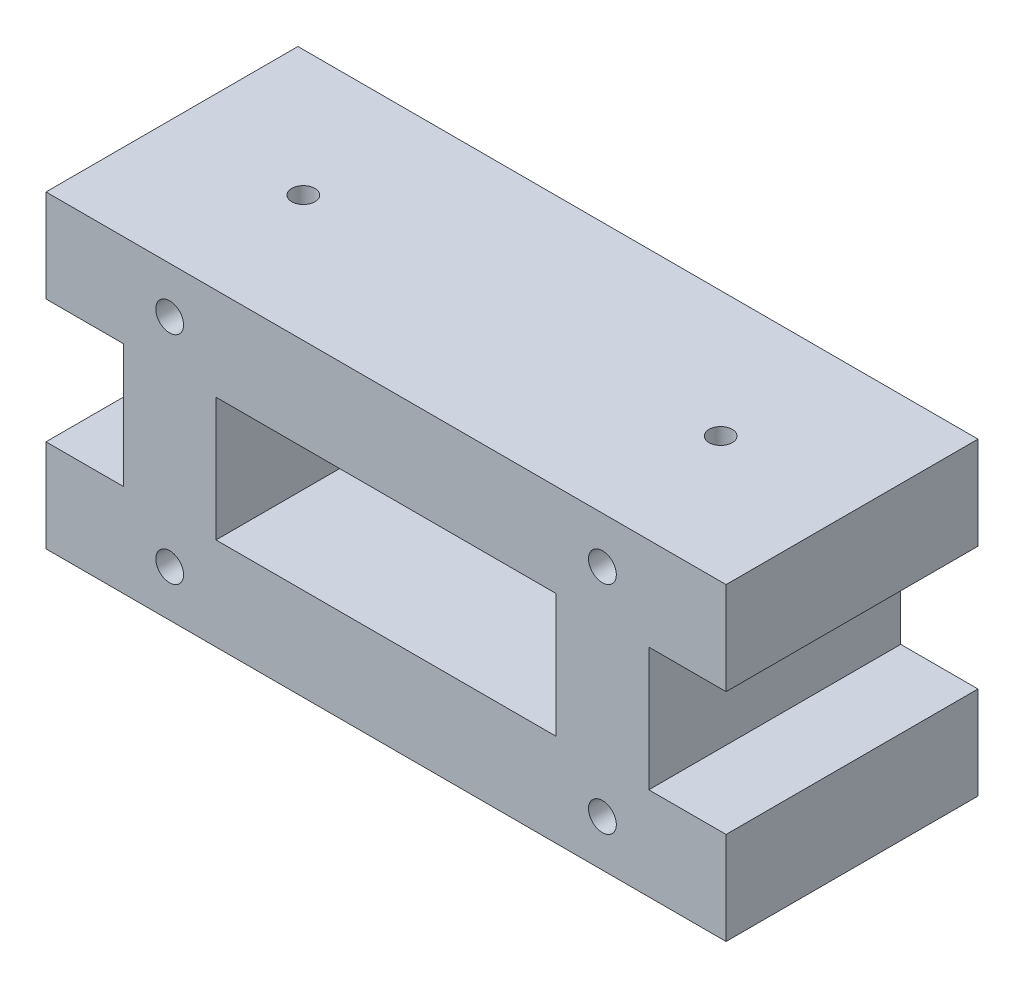
SolidWorks part; units mm, degrees
ref_plane "前视基准面" through (0, 0, 0) normal (0, 0, 1) x (1, 0, 0)
ref_plane "上视基准面" through (0, 0, 0) normal (0, 1, 0) x (1, 0, 0)
ref_plane "右视基准面" through (0, 0, 0) normal (1, 0, 0) x (0, 0, -1)
other "Configuration Table"
sketch "草图1" plane through (0, 0, 0) normal (0, 0, 1) x (1, 0, 0)
  line L0 (8, 7) -> (36, 7) construction
  line L5 (0, 10) -> (44, 10)
  line L6 (0, 10) -> (0, -10)
  line L7 (0, -10) -> (44, -10)
  line L8 (44, 10) -> (44, -10)
  line L9 (36, 7) -> (44, 7) construction
  line L11 (8, 7) -> (0, 7) construction
  line L12 (0, 4) -> (44, 4)
  line L13 (0, -4) -> (44, -4)
  line L14 (5, 4) -> (5, -4)
  line L15 (11, 4) -> (11, -4)
  line L16 (33, 4) -> (33, -4)
  line L17 (39, 4) -> (39, -4)
  circle A11 centre (8, 7) radius 0.9
  circle A13 centre (36, 7) radius 0.9
  circle A14 centre (8, -7) radius 0.9
  circle A15 centre (36, -7) radius 0.9
  dimension "D1" = 20
  dimension "D2" = 44
  dimension "D4" = 3
  dimension "D5" = 3
  dimension "D3" = 1.8
  dimension "D6" = 28
  dimension "D7" = 3
  dimension "D8" = 3
  dimension "D9" = 3
  dimension "D10" = 3
  dimension "D11" = 3
  dimension "D12" = 3
extrude "凸台-拉伸1" add sketch "草图1" along normal blind 16.3 contours L6 L12 L8 L5 A13 A11 | L13 L6 L7 L8 A15 A14 | L15 L12 L14 L13 | L17 L12 L16 L13 region at (22, 7, 0) region at (22, -7, 0) region at (8, 0, 0) region at (36, 0, 0)
sketch "草图2" plane through (0, 10, 0) normal (0, 1, 0) x (1, 0, 0)
  line L0 (8.5, -16.3) -> (8.5, 0)
  line L1 (0, -16.3) -> (44, -16.3) construction
  line L2 (0, 0) -> (44, 0) construction
  line L3 (0, -16.3) -> (0, 0) construction
  line L4 (44, -16.3) -> (44, 0) construction
  circle A0 centre (8.5, -8.15) radius 0.75
  circle A1 centre (35.5, -8.15) radius 0.75
  point P8 (0, 0)
  dimension "D1" = 1.5
  dimension "D2" = 8.5
  dimension "D3" = 8.5
extrude "切除-拉伸1" cut sketch "草图2" against normal blind 4 contours A0 | A1
extrude "切除-拉伸2" cut sketch "草图2<3>" along normal blind 4 from surface contours A0 | A1 starting at face at (22, -10, 8.15)
sketch "草图2<3>" plane through (0, 10, 0) normal (0, 1, 0) x (1, 0, 0) same geometry as "草图2"
